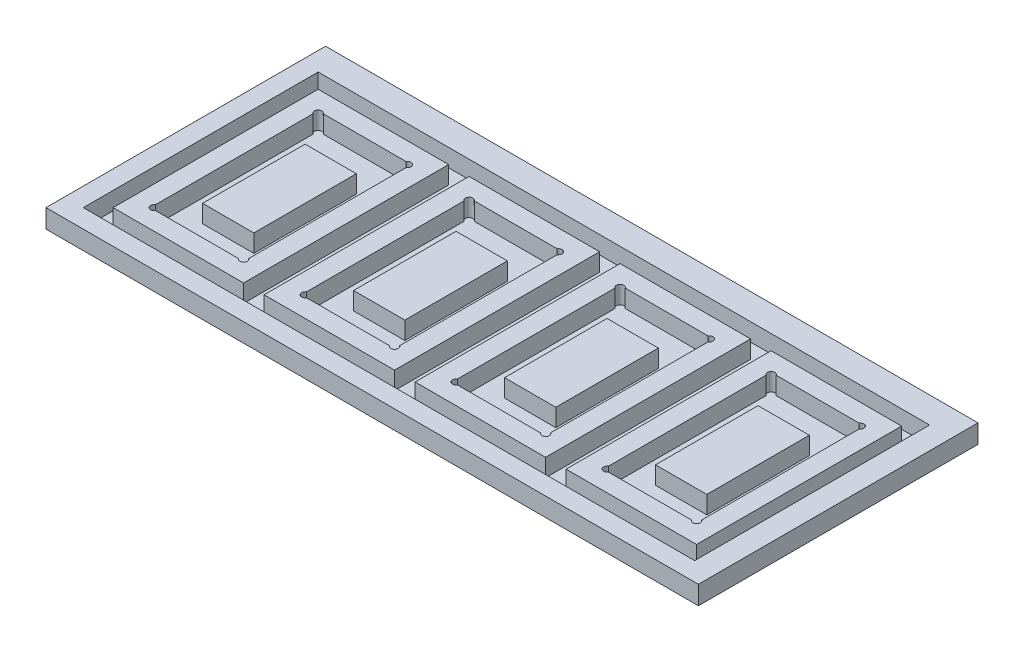
SolidWorks part; units mm, degrees
material "6061 Alloy"
ref_plane "Front Plane" through (0, 0, 0) normal (0, 0, 1) x (1, 0, 0)
ref_plane "Top Plane" through (0, 0, 0) normal (0, 1, 0) x (1, 0, 0)
ref_plane "Right Plane" through (0, 0, 0) normal (1, 0, 0) x (0, 0, -1)
sketch "Sketch1" plane through (0, 0, 0) normal (0, 1, 0) x (1, 0, 0)
  line L1 (-175, -75) -> (175, -75)
  line L2 (-175, -75) -> (-175, 75)
  line L3 (-175, 75) -> (175, 75)
  line L4 (175, -75) -> (175, 75)
  line L5 (-175, -75) -> (175, 75) construction
  line L6 (-175, 75) -> (175, -75) construction
  point P0 (0, 0)
  dimension "D1" = 350
  dimension "D2" = 150
extrude "Boss-Extrude1" add sketch "Sketch1" along normal blind 10
sketch "Sketch2" plane through (0, 10, 0) normal (0, 1, 0) x (1, 0, 0)
  line L0 (98.7562, 43) -> (143.2438, 43)
  line L1 (86, -57) -> (156, -57)
  line L2 (86, -57) -> (86, 53)
  line L3 (86, 53) -> (156, 53)
  line L4 (156, -57) -> (156, 53)
  line L5 (86, -57) -> (156, 53) construction
  line L6 (86, 53) -> (156, -57) construction
  line L7 (146, -44.2438) -> (146, 40.2438)
  line L8 (98.7562, -47) -> (143.2438, -47)
  line L9 (96, -44.2438) -> (96, 40.2438)
  line L10 (96, 43) -> (146, 43) construction
  line L11 (96, -47) -> (96, 43) construction
  line L12 (146, -47) -> (146, 43) construction
  line L13 (96, -47) -> (146, -47) construction
  line L14 (-175, -75) -> (175, -75) construction
  line L15 (108, 24) -> (135.5, 24)
  line L16 (108, 24) -> (108, -31)
  line L17 (108, -31) -> (135.5, -31)
  line L18 (135.5, 24) -> (135.5, -31)
  line L24 (96, -47) -> (96, -44.2438) construction
  line L25 (96, -47) -> (98.7562, -47) construction
  line L26 (143.2438, -47) -> (146, -47) construction
  line L27 (146, -47) -> (146, -44.2438) construction
  line L28 (96, 43) -> (97.0607, 41.9393) construction
  line L29 (146, 43) -> (146, 40.2438) construction
  line L30 (96, 43) -> (98.7562, 43) construction
  line L31 (96, 43) -> (96, 40.2438) construction
  line L32 (146, 43) -> (144.9393, 41.9393) construction
  line L33 (146, -47) -> (144.9393, -45.9393) construction
  line L34 (96, -47) -> (97.0607, -45.9393) construction
  line L35 (5, 53) -> (75, 53)
  line L36 (17.7562, 43) -> (62.2438, 43)
  line L37 (75, -57) -> (75, 53)
  line L38 (65, -44.2438) -> (65, 40.2438)
  line L39 (15, -44.2438) -> (15, 40.2438)
  line L40 (5, -57) -> (5, 53)
  line L41 (5, -57) -> (75, -57)
  line L42 (17.7562, -47) -> (62.2438, -47)
  line L43 (27, 24) -> (27, -31)
  line L44 (27, -31) -> (54.5, -31)
  line L45 (54.5, 24) -> (54.5, -31)
  line L46 (27, 24) -> (54.5, 24)
  line L47 (-76, 53) -> (-6, 53)
  line L48 (-63.2438, 43) -> (-18.7562, 43)
  line L49 (-6, -57) -> (-6, 53)
  line L50 (-16, -44.2438) -> (-16, 40.2438)
  line L51 (-66, -44.2438) -> (-66, 40.2438)
  line L52 (-76, -57) -> (-76, 53)
  line L53 (-76, -57) -> (-6, -57)
  line L54 (-63.2438, -47) -> (-18.7562, -47)
  line L55 (-54, 24) -> (-54, -31)
  line L56 (-54, -31) -> (-26.5, -31)
  line L57 (-26.5, 24) -> (-26.5, -31)
  line L58 (-54, 24) -> (-26.5, 24)
  line L59 (-157, 53) -> (-87, 53)
  line L60 (-144.2438, 43) -> (-99.7562, 43)
  line L61 (-87, -57) -> (-87, 53)
  line L62 (-97, -44.2438) -> (-97, 40.2438)
  line L63 (-147, -44.2438) -> (-147, 40.2438)
  line L64 (-157, -57) -> (-157, 53)
  line L65 (-157, -57) -> (-87, -57)
  line L66 (-144.2438, -47) -> (-99.7562, -47)
  line L67 (-135, 24) -> (-135, -31)
  line L68 (-135, -31) -> (-107.5, -31)
  line L69 (-107.5, 24) -> (-107.5, -31)
  line L70 (-135, 24) -> (-107.5, 24)
  line L73 (-175, 75) -> (-175, -75) construction
  line L79 (-165, 61) -> (163, 61)
  line L80 (-165, 61) -> (-165, -65)
  line L81 (-165, -65) -> (163, -65)
  line L82 (163, 61) -> (163, -65)
  arc A4 (146, 40.2438) -> (143.2438, 43) centre (144.9393, 41.9393) ccw
  arc A5 (98.7562, 43) -> (96, 40.2438) centre (97.0607, 41.9393) ccw
  arc A6 (96, -44.2438) -> (98.7562, -47) centre (97.0607, -45.9393) ccw
  arc A7 (143.2438, -47) -> (146, -44.2438) centre (144.9393, -45.9393) ccw
  arc A8 (65, 40.2438) -> (62.2438, 43) centre (63.9393, 41.9393) ccw
  arc A9 (17.7562, 43) -> (15, 40.2438) centre (16.0607, 41.9393) ccw
  arc A10 (62.2438, -47) -> (65, -44.2438) centre (63.9393, -45.9393) ccw
  arc A11 (15, -44.2438) -> (17.7562, -47) centre (16.0607, -45.9393) ccw
  arc A12 (-16, 40.2438) -> (-18.7562, 43) centre (-17.0607, 41.9393) ccw
  arc A13 (-63.2438, 43) -> (-66, 40.2438) centre (-64.9393, 41.9393) ccw
  arc A14 (-18.7562, -47) -> (-16, -44.2438) centre (-17.0607, -45.9393) ccw
  arc A15 (-66, -44.2438) -> (-63.2438, -47) centre (-64.9393, -45.9393) ccw
  arc A16 (-97, 40.2438) -> (-99.7562, 43) centre (-98.0607, 41.9393) ccw
  arc A17 (-144.2438, 43) -> (-147, 40.2438) centre (-145.9393, 41.9393) ccw
  arc A18 (-99.7562, -47) -> (-97, -44.2438) centre (-98.0607, -45.9393) ccw
  arc A19 (-147, -44.2438) -> (-144.2438, -47) centre (-145.9393, -45.9393) ccw
  dimension "D3" = 4
  dimension "D13" = 45
  dimension "D17" = 4
  dimension "D22" = 4
  dimension "D23" = 4
  dimension "D1" = 110
  dimension "D4" = 55
  dimension "D5" = 27.5
  dimension "D6" = 8
  dimension "D7" = 12
  dimension "D8" = 7
  dimension "D9" = 19
  dimension "D10" = 70
  dimension "D11" = 16
  dimension "D12" = 10.5
  dimension "D14" = 1.5
  dimension "D15" = 45
  dimension "D16" = 1.5
  dimension "D18" = 1.5
  dimension "D19" = 45
  dimension "D20" = 1.5
  dimension "D21" = 45
  dimension "D25" = 11
  dimension "D26" = 10
  dimension "D27" = 8
  dimension "D28" = 8
  dimension "D29" = 10
  dimension "D2" = 10
  dimension "D24" = 4
extrude "Cut-Extrude1" cut sketch "Sketch2" against normal blind 9.5 contours L82 L79 L80 L81 L65 L64 L59 L61 L53 L52 L47 L49 L41 L40 L35 L37 L4 L1 L2 L3 | L63 A19 L66 A18 L62 A16 L60 A17 L67 L70 L69 L68 | L51 A15 L54 A14 L50 A12 L48 A13 L55 L58 L57 L56 | L39 A11 L42 A10 L38 A8 L36 A9 L43 L46 L45 L44 | L8 A7 L7 A4 L0 A5 L9 A6 L15 L18 L17 L16 region at (121, 10, -41.9449) region at (40, 10, -41.9449) region at (-41, 10, -41.9449) region at (-122, 10, -41.9449) region at (-2.4628, 10, 2)
